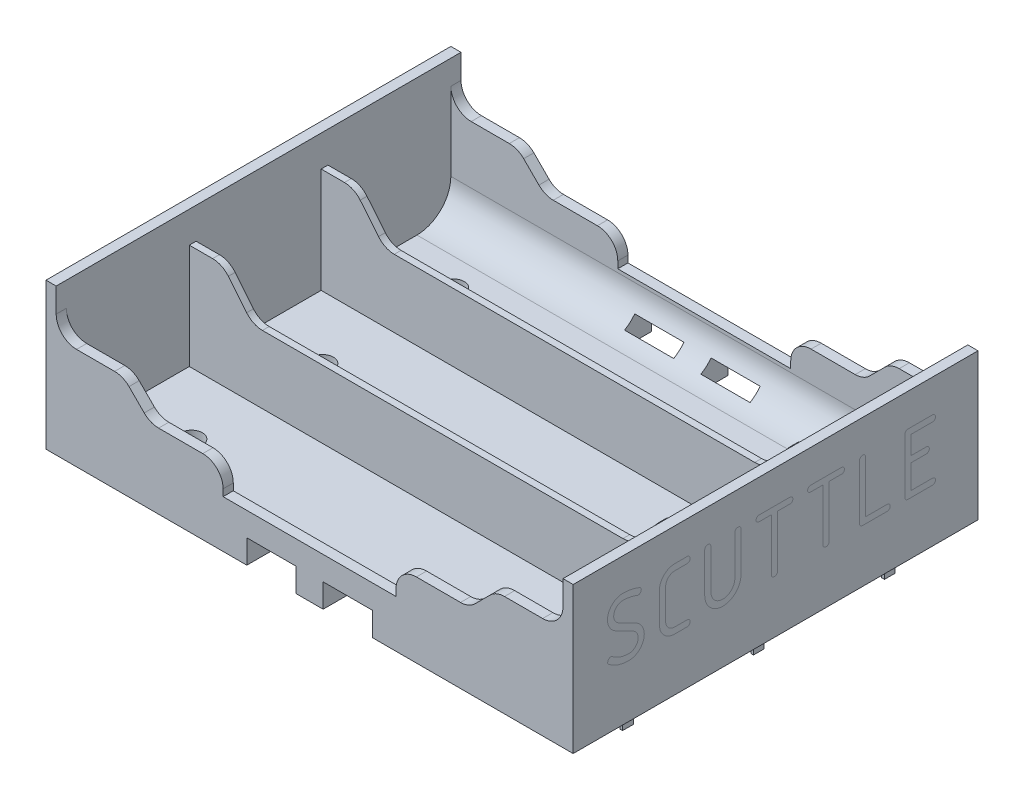
SolidWorks part; units mm, degrees
ref_plane "Front Plane" through (0, 0, 0) normal (0, 0, 1) x (1, 0, 0)
ref_plane "Top Plane" through (0, 0, 0) normal (0, 1, 0) x (1, 0, 0)
ref_plane "Right Plane" through (0, 0, 0) normal (1, 0, 0) x (0, 0, -1)
ref_plane "Plane1" through (0, 0, 0) normal (0, -1, 0) x (1, 0, 0)
sketch "Sketch1" plane through (0, 0, 0) normal (0, -1, 0) x (1, 0, 0)
  line L0 (-38.862, 29.845) -> (-38.862, -29.845)
  line L1 (-38.862, -29.845) -> (38.862, -29.845)
  line L2 (38.862, -29.845) -> (38.862, 29.845)
  line L3 (38.862, 29.845) -> (-38.862, 29.845)
  line L4 (-38.862, 29.845) -> (38.862, -29.845) construction
  dimension "D1" = 77.724
  dimension "D2" = 59.69
extrude "Boss-Extrude1" add sketch "Sketch1" against normal blind 21.59
sketch "Sketch2" plane through (0, 0, 0) normal (0, -1, 0) x (1, 0, 0)
  line L0 (-35.9918, 0.7874) -> (-35.9918, -0.7874)
  line L1 (-35.9918, -0.7874) -> (-36.3982, -0.7874)
  line L2 (-36.3982, -0.7874) -> (-36.3982, 0.7874)
  line L3 (-36.3982, 0.7874) -> (-35.9918, 0.7874)
extrude "Boss-Extrude2" add sketch "Sketch2" along normal blind 3.175
sketch "Sketch3" plane through (0, 0, 0) normal (0, -1, 0) x (1, 0, 0)
  line L0 (36.3982, 0.7874) -> (36.3982, -0.7874)
  line L1 (36.3982, -0.7874) -> (35.9918, -0.7874)
  line L2 (35.9918, -0.7874) -> (35.9918, 0.7874)
  line L3 (35.9918, 0.7874) -> (36.3982, 0.7874)
extrude "Boss-Extrude3" add sketch "Sketch3" along normal blind 3.175
sketch "Sketch4" plane through (0, 0, 0) normal (0, -1, 0) x (1, 0, 0)
  line L0 (-35.9918, 20.0914) -> (-35.9918, 18.5166)
  line L1 (-35.9918, 18.5166) -> (-36.3982, 18.5166)
  line L2 (-36.3982, 18.5166) -> (-36.3982, 20.0914)
  line L3 (-36.3982, 20.0914) -> (-35.9918, 20.0914)
extrude "Boss-Extrude4" add sketch "Sketch4" along normal blind 3.175
sketch "Sketch5" plane through (0, 0, 0) normal (0, -1, 0) x (1, 0, 0)
  line L0 (36.3982, 20.0914) -> (36.3982, 18.5166)
  line L1 (36.3982, 18.5166) -> (35.9918, 18.5166)
  line L2 (35.9918, 18.5166) -> (35.9918, 20.0914)
  line L3 (35.9918, 20.0914) -> (36.3982, 20.0914)
extrude "Boss-Extrude5" add sketch "Sketch5" along normal blind 3.175
sketch "Sketch6" plane through (0, 0, 0) normal (0, -1, 0) x (1, 0, 0)
  line L0 (36.3982, -18.5166) -> (36.3982, -20.0914)
  line L1 (36.3982, -20.0914) -> (35.9918, -20.0914)
  line L2 (35.9918, -20.0914) -> (35.9918, -18.5166)
  line L3 (35.9918, -18.5166) -> (36.3982, -18.5166)
extrude "Boss-Extrude6" add sketch "Sketch6" along normal blind 3.175
sketch "Sketch7" plane through (0, 0, 0) normal (0, -1, 0) x (1, 0, 0)
  line L0 (-35.9918, -18.5166) -> (-35.9918, -20.0914)
  line L1 (-35.9918, -20.0914) -> (-36.3982, -20.0914)
  line L2 (-36.3982, -20.0914) -> (-36.3982, -18.5166)
  line L3 (-36.3982, -18.5166) -> (-35.9918, -18.5166)
extrude "Boss-Extrude7" add sketch "Sketch7" along normal blind 3.175
hole_wizard "#4 Clearance Hole1" positions "Sketch9" profile "Sketch8" hole size "#4" standard "ANSI Inch"
sketch "Sketch9" plane through (0, 0, 0) normal (0, -1, 0) x (-1, 0, 0)
  point P0 (27.94, 19.304)
  point P1 (27.94, 0)
  point P2 (-27.686, 19.304)
  point P3 (-27.686, 0)
  point P4 (-27.686, -19.304)
  point P5 (27.94, -19.304)
sketch "Sketch8" plane through (-27.94, 0, -19.304) normal (1, 0, 0) x (0, 0, -1)
  line L0 (0, 0) -> (0, 5.08)
  line L1 (0, 5.08) -> (1.6002, 5.08)
  line L2 (1.6002, 5.08) -> (1.6002, 0)
  line L5 (1.6002, 0) -> (0, 0)
  line L10 (0, 5.08) -> (-1.6002, 5.08) construction
  line L11 (0, -6.35) -> (0, 107.95) construction
  dimension "Hole Dia." = 3.2004
  dimension "Hole Depth" = 5.08
  dimension "Drill Angle" = 180
shell "Shell1" thickness 1.5 removed face at (0, 21.59, 0)
fillet "Fillet1" radius 5 2 edges at (0, 1.5, -28.345) (0, 1.5, 28.345)
sketch "Sketch10" plane through (0, 0, -29.845) normal (0, 0, -1) x (-1, 0, 0)
  line L0 (0, 7) -> (12.75, 7)
  line L1 (12.75, 7) -> (12.75, 11)
  line L2 (12.75, 11) -> (23.5, 11)
  line L3 (23.5, 11) -> (27.5, 15)
  line L4 (27.5, 15) -> (37.362, 15)
  line L5 (37.362, 21.59) -> (37.362, 6.5) construction
  line L6 (37.362, 15) -> (37.362, 21.59)
  line L7 (0, 0) -> (0, 21.59) construction
  line L8 (38.862, 21.59) -> (-38.862, 21.59) construction
  line L9 (38.862, 0) -> (-38.862, 0) construction
  line L10 (0, 7) -> (0, 21.59)
  line L11 (0, 21.59) -> (37.362, 21.59)
  dimension "D1" = 25.5
  dimension "D2" = 47
  dimension "D3" = 55
  dimension "D4" = 15
  dimension "D5" = 11
  dimension "D6" = 7
extrude "Cut-Extrude3" cut sketch "Sketch10" against normal through all contours L10 L11 L6 L4 L3 L2 L1 L0
mirror "Mirror1" about plane through (0, 0, 0) normal (1, 0, 0) of "Cut-Extrude3"
sketch "Sketch11" plane through (0, 1.5, 0) normal (0, 1, 0) x (1, 0, 0)
  line L1 (-37.362, 23.345) -> (37.362, 23.345)
  line L2 (-37.362, 23.345) -> (-37.362, -23.345)
  line L3 (-37.362, -23.345) -> (37.362, -23.345)
  line L4 (37.362, 23.345) -> (37.362, -23.345)
extrude "Cut-Extrude4" cut sketch "Sketch11" along normal through all
sketch "Sketch12" plane through (0, 1.5, 0) normal (0, 1, 0) x (1, 0, 0)
  line L0 (-37.362, -23.345) -> (-37.362, 23.345) construction
  line L1 (-37.362, 10.22) -> (37.362, 10.22)
  line L2 (-37.362, 10.22) -> (-37.362, 9.22)
  line L3 (-37.362, 9.22) -> (37.362, 9.22)
  line L4 (37.362, 10.22) -> (37.362, 9.22)
  line L5 (37.362, 23.345) -> (37.362, -23.345) construction
  line L6 (0, 0) -> (37.362, 0) construction
  line L7 (37.362, 29.845) -> (37.362, -29.845) construction
  dimension "D1" = 20.44
  dimension "D2" = 1
extrude "Boss-Extrude8" add sketch "Sketch12" along normal blind 15.5
sketch "Sketch13" plane through (0, 0, -9.22) normal (0, 0, 1) x (1, 0, 0)
  line L0 (-32.5, 17) -> (-28, 11.5)
  line L1 (-37.362, 17) -> (37.362, 17) construction
  line L2 (-28, 11.5) -> (28, 11.5)
  line L3 (28, 11.5) -> (32.5, 17)
  line L4 (-32.5, 17) -> (32.5, 17)
  point P4 (0, 11.5)
  point P7 (0, 17)
  dimension "D1" = 56
  dimension "D2" = 65
  dimension "D3" = 5.5
extrude "Cut-Extrude5" cut sketch "Sketch13" against normal up to next
mirror "Mirror2" about plane through (0, 0, 0) normal (0, 0, 1) of "Cut-Extrude5", "Boss-Extrude8"
fillet "Fillet2" radius 3 24 edges at (-37.362, 15, 29.095) (-28, 11.5, -9.72) (-32.5, 17, -9.72) (-32.5, 17, 9.72) (-28, 11.5, 9.72) (-37.362, 15, -29.095) (-27.5, 15, -29.095) (-23.5, 11, -29.095) (-12.75, 11, -29.095) (12.75, 11, -29.095) (23.5, 11, -29.095) (27.5, 15, -29.095) (37.362, 15, -29.095) (28, 11.5, -9.72) (32.5, 17, -9.72) (32.5, 17, 9.72) (28, 11.5, 9.72) (37.362, 15, 29.095) (23.5, 11, 29.095) (27.5, 15, 29.095) (12.75, 11, 29.095) (-12.75, 11, 29.095) (-23.5, 11, 29.095) (-27.5, 15, 29.095)
sketch "Sketch14" plane through (0, 1.5, 0) normal (0, 1, 0) x (1, 0, 0)
  circle A0 centre (21.1599, 16.5354) radius 1.9057
  text T0 "+"
extrude "Cut-Extrude6" cut sketch "Sketch14" against normal blind 0.2
pattern_linear "LPattern1" count 3 spacing 17.5 along (0, 0, 1) of "Cut-Extrude6"
ref_plane "Plane2" through (0, 0, -18.7825) normal (0, 0, 1) x (1, 0, 0)
ref_plane "Plane3" through (0, 0, 0.5) normal (0, 0, 1) x (1, 0, 0)
ref_plane "Plane4" through (0, 0, 20.0325) normal (0, 0, 1) x (1, 0, 0)
ref_plane "Plane5" through (0, 9.5, 0) normal (0, 1, 0) x (1, 0, 0)
ref_axis "Axis1" through (-41.0982, 9.5, -18.7825) along (1, 0, 0)
ref_axis "Axis2" through (-41.0982, 9.5, 0.5) along (1, 0, 0)
ref_axis "Axis3" through (-41.0982, 9.5, 20.0325) along (1, 0, 0)
sketch "Sketch15" plane through (38.862, 0, 0) normal (1, 0, 0) x (0, 0, -1)
  text T0 "SCUTTLE" font "DS ISO 1" height 9
split line "Split Line1"
sketch "Sketch16" plane through (0, 0, 0) normal (0, -1, 0) x (1, 0, 0)
  line L0 (38.862, 29.845) -> (-38.862, 29.845) construction
  line L1 (-9.25, 29.845) -> (-2, 29.845)
  line L2 (-9.25, 29.845) -> (-9.25, 25.845)
  line L3 (-9.25, 25.845) -> (-2, 25.845)
  line L4 (-2, 29.845) -> (-2, 25.845)
  line L5 (-2, 25.845) -> (2, 25.845) construction
  line L6 (2, 29.845) -> (9.25, 29.845)
  line L7 (2, 29.845) -> (2, 25.845)
  line L8 (2, 25.845) -> (9.25, 25.845)
  line L9 (9.25, 29.845) -> (9.25, 25.845)
  point P10 (0, 25.845)
  dimension "D1" = 18.5
  dimension "D2" = 4
  dimension "D3" = 4
extrude "Cut-Extrude7" cut sketch "Sketch16" against normal blind 3.5
mirror "Mirror3" about plane through (0, 0, 0) normal (0, 0, 1) of "Cut-Extrude7"
